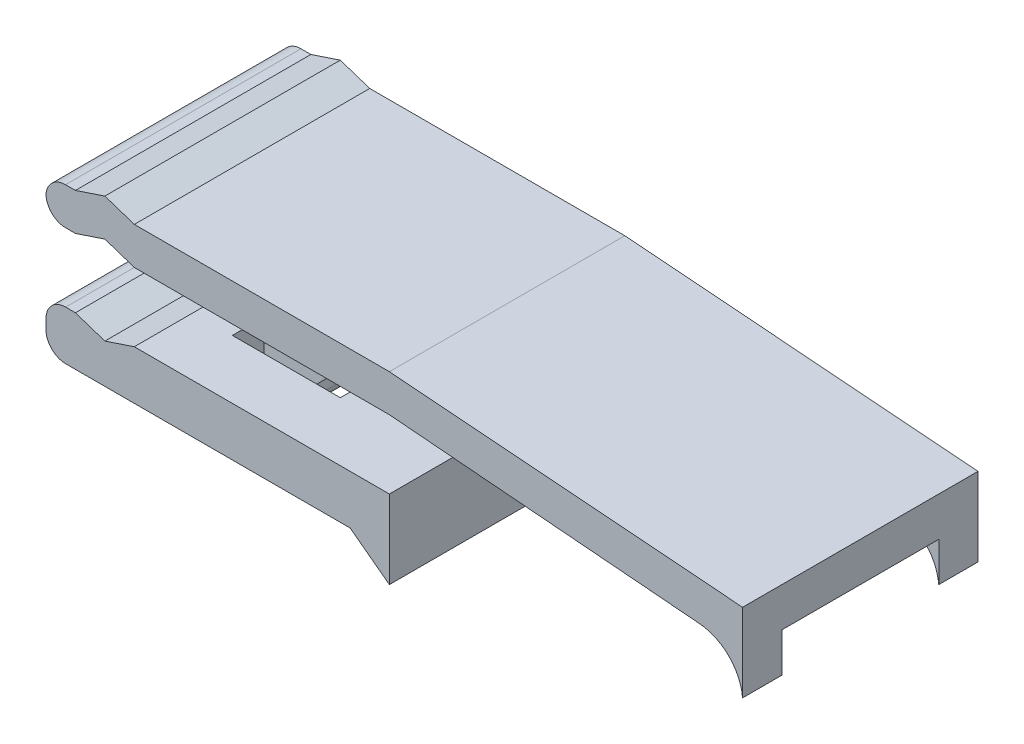
SolidWorks part; units mm, degrees
ref_plane "Front Plane" through (0, 0, 0) normal (0, 0, 1) x (1, 0, 0)
ref_plane "Top Plane" through (0, 0, 0) normal (0, 1, 0) x (1, 0, 0)
ref_plane "Right Plane" through (0, 0, 0) normal (1, 0, 0) x (0, 0, -1)
sketch "Sketch1" plane through (0, 0, 0) normal (0, 0, 1) x (1, 0, 0)
  line L0 (0, 0) -> (0, 4) construction
  line L1 (0, 0) -> (-18, 0) construction
  line L2 (0, 4) -> (-18, 5.4)
  line L3 (-18, 5.4) -> (-31, 5.4)
  line L4 (-31, 5.4) -> (-32.5, 5.9)
  line L5 (-32.5, 5.9) -> (-34, 5.4)
  line L6 (-34, 5.4) -> (-35.5, 5.4)
  line L7 (-35.5, 5.4) -> (-35.5, 3.5)
  line L8 (-35.5, -2.5) -> (-20, -2.5)
  line L9 (-20, -2.5) -> (-18, -4)
  line L10 (-35.5, 3.5) -> (-34, 3.5)
  line L11 (-34, 3.5) -> (-32.5, 4)
  line L12 (-18, 0) -> (-18, -4)
  line L13 (-18, 0) -> (-31, 0)
  line L14 (-31, 0) -> (-32.5, -0.5)
  line L15 (-32.5, -0.5) -> (-34, 0)
  line L16 (-34, 0) -> (-35.5, 0)
  line L17 (-35.5, 0) -> (-35.5, -2.5)
  line L18 (-32.5, 4) -> (-31, 3.5)
  line L19 (-31, 3.5) -> (-18, 3.5)
  line L20 (-18, 0) -> (-18, 5.4) construction
  line L21 (-18, 3.5) -> (0, 2)
  line L22 (0, 2) -> (0, 4)
  dimension "D1" = 13
  dimension "D2" = 18
  dimension "D3" = 0.5
  dimension "D4" = 2.5
  dimension "D5" = 1.5
  dimension "D6" = 3.5
  dimension "D7" = 1.5
  dimension "D8" = 2
  dimension "D9" = 0.5
  dimension "D10" = 2
  dimension "D11" = 0.5
  dimension "D12" = 1.9
  dimension "D13" = 1.5
  dimension "D15" = 3
  dimension "D16" = 1.5
extrude "Boss-Extrude1" add sketch "Sketch1" along normal blind 12
sketch "Sketch2" plane through (0, -2.5, 0) normal (0, -1, 0) x (1, 0, 0)
  line L0 (-20, 12) -> (-20, 0) construction
  line L1 (-29, 9) -> (-23.5, 9)
  line L2 (-29, 9) -> (-29, 3)
  line L3 (-29, 3) -> (-23.5, 3)
  line L4 (-23.5, 9) -> (-23.5, 3)
  line L7 (-20, 6) -> (-35.5, 6) construction
  line L8 (-35.5, 12) -> (-35.5, 0) construction
  point P9 (-23.5, 6)
  dimension "D1" = 3.5
  dimension "D2" = 5.5
  dimension "D3" = 6
extrude "Cut-Extrude1" cut sketch "Sketch2" against normal blind 3
sketch "Sketch3" plane through (0, 0, 3) normal (0, 0, 1) x (1, 0, 0)
  line L0 (-23.5, 0) -> (-25.5, -2)
  line L1 (-25.5, -2) -> (-25.5, -2.5)
  line L2 (-35.5, -2.5) -> (-20, -2.5) construction
  line L3 (-25.5, -2.5) -> (-23.5, -2.5)
  line L4 (-23.5, -2.5) -> (-23.5, 0)
  dimension "D1" = 0.5
  dimension "D2" = 2
extrude "Boss-Extrude2" add sketch "Sketch3" along normal up to surface (6 mm away) up to face at (-26.25, -1.25, 9)
sketch "Sketch4" plane through (0, 0, 12) normal (0, 0, 1) x (1, 0, 0)
  line L0 (-26.7, -2) -> (-24.7, 0)
  line L1 (-18, 0) -> (-31, 0) construction
  line L2 (-24.7, 0) -> (-24.7, 0.4)
  line L3 (-24.7, 0.4) -> (-26.2, 0.4)
  line L4 (-26.2, 0.4) -> (-26.2, 1.2)
  line L5 (-31, 3.5) -> (-18, 3.5) construction
  line L6 (-26.7, -2) -> (-26.7, -3)
  line L7 (-26.7, -3) -> (-27.9, -3)
  line L8 (-27.9, -3) -> (-27.9, 1.2)
  line L10 (-25.5, -2) -> (-25.5, -2.5) construction
  line L11 (-26.2, 1.2) -> (-29.7054, 3.2238) construction
  line L12 (-26.2, 1.2) -> (-23.9, 3.5)
  line L13 (-27.6722, 2.05) -> (-26.8351, 3.5)
  line L15 (-35.5, -2.5) -> (-20, -2.5) construction
  line L16 (-26.8351, 3.5) -> (-23.9, 3.5)
  arc A0 (-27.6722, 2.05) -> (-27.9, 1.2) centre (-26.2, 1.2) ccw
  dimension "D1" = 1.5
  dimension "D2" = 1.2
  dimension "D3" = 45
  dimension "D4" = 0.4
  dimension "D5" = 1.2
  dimension "D6" = 1
  dimension "D7" = 2
  dimension "D8" = 0.8
  dimension "D9" = 30
  dimension "D11" = 0.8
  dimension "D13" = 2.9
  dimension "D14" = 3.1
extrude "Boss-Extrude3" add sketch "Sketch4" against normal mid plane 5 from offset 6 offset against normal yes
fillet "Fillet7" radius 1 1 edges at (-35.5, 0, 6)
fillet "Fillet8" radius 1 1 edges at (-35.5, 3.5, 6)
fillet "Fillet10" radius 1 1 edges at (-35.5, 5.4, 6)
fillet "Fillet11" radius 1 1 edges at (-35.5, -2.5, 6)
sketch "Sketch5" plane through (0, 0, 12) normal (0, 0, 1) x (1, 0, 0)
  line L0 (0, 2) -> (0, 0)
  line L1 (-18, 3.5) -> (0, 2) construction
  line L2 (-2.1818, 2.1818) -> (0, 2)
  arc A0 (-2.1818, 2.1818) -> (0, 0) centre (-2.3802, -0.1983) cw
extrude "Boss-Extrude4" add sketch "Sketch5" against normal blind 2
extrude "Boss-Extrude5" add sketch "Sketch5<2>" along normal blind 2 from offset 12 offset against normal yes
sketch "Sketch5<2>" plane through (0, 0, 12) normal (0, 0, 1) x (1, 0, 0) same geometry as "Sketch5"
fillet "Fillet12" radius 0.5 2 edges at (-26.7, -3, 6) (-27.9, -3, 6)
fillet "Fillet13" radius 0.5 1 edges at (-26.2, 1.2, 6)
